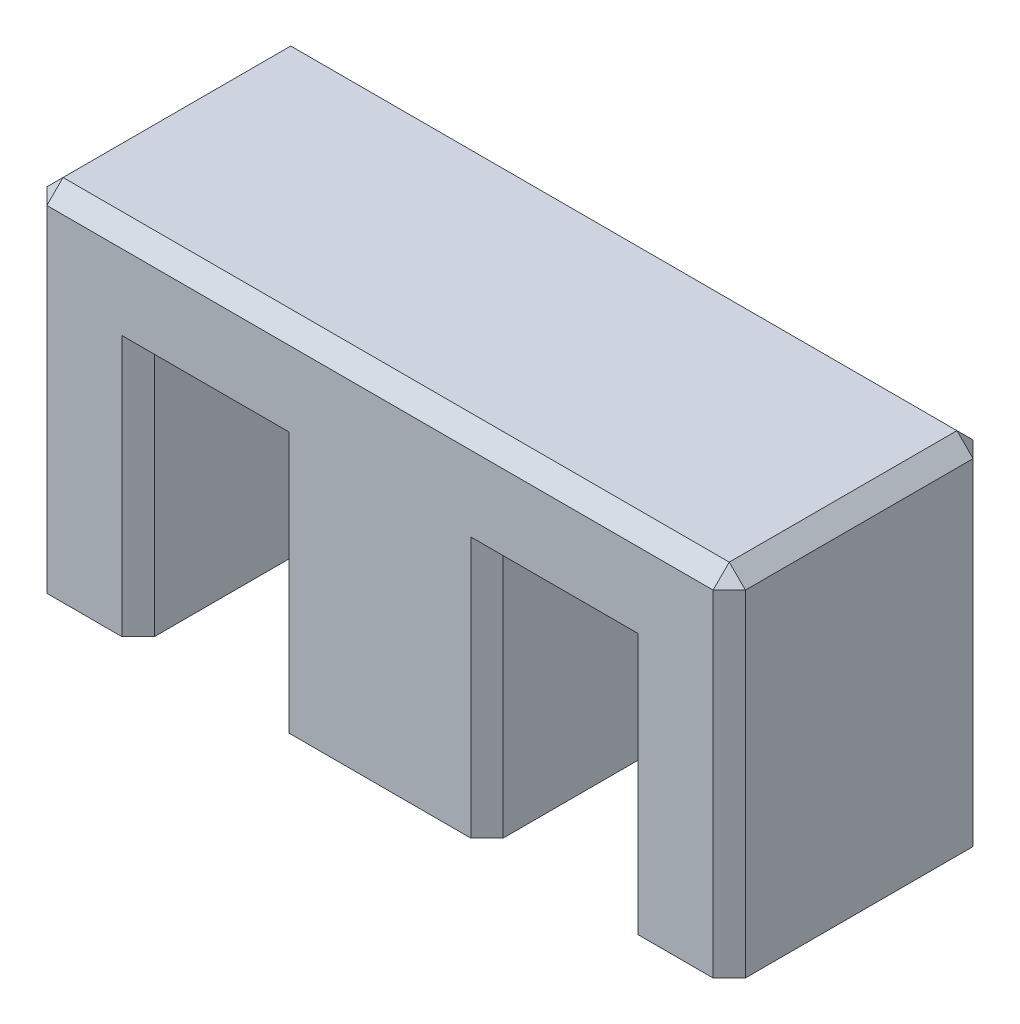
SolidWorks part; units mm, degrees
material "Ductile Iron"
ref_plane "Front Plane" through (0, 0, 0) normal (0, 0, 1) x (1, 0, 0)
ref_plane "Top Plane" through (0, 0, 0) normal (0, 1, 0) x (1, 0, 0)
ref_plane "Right Plane" through (0, 0, 0) normal (1, 0, 0) x (0, 0, -1)
sketch "Sketch1" plane through (0, 0, 0) normal (0, 0, 1) x (1, 0, 0)
  line L0 (0, 33.0544) -> (0, -29.4507) construction
  line L1 (43.25, 31.1735) -> (-43.25, 31.1735)
  line L2 (-43.25, 31.1735) -> (-43.25, -12.4265)
  line L3 (-43.25, -12.4265) -> (-29.95, -12.4265)
  line L4 (-29.95, -12.4265) -> (-29.95, 17.8735)
  line L5 (-29.95, 17.8735) -> (-13.25, 17.8735)
  line L6 (-13.25, 17.8735) -> (-13.25, -12.4265)
  line L7 (-13.25, -12.4265) -> (13.25, -12.4265)
  line L8 (13.25, 17.8735) -> (13.25, -12.4265)
  line L9 (29.95, 17.8735) -> (13.25, 17.8735)
  line L10 (29.95, -12.4265) -> (29.95, 17.8735)
  line L11 (43.25, -12.4265) -> (29.95, -12.4265)
  line L12 (43.25, 31.1735) -> (43.25, -12.4265)
  point P12 (0, -12.4265)
  point P13 (0, 31.1735)
  dimension "D1" = 86.5
  dimension "D2" = 43.6
  dimension "D3" = 26.5
  dimension "D4" = 13.3
  dimension "D5" = 13.3
extrude "Boss-Extrude1" add sketch "Sketch1" along normal mid plane 32.2
chamfer "Chamfer1" distance 2 angle 45 20 edges at (43.25, 31.1735, 0) (43.25, 9.3735, 16.1) (0, 31.1735, 16.1) (-43.25, 9.3735, 16.1) (-43.25, 31.1735, 0) (-43.25, 9.3735, -16.1) (0, 31.1735, -16.1) (43.25, 9.3735, -16.1) (13.25, 2.7235, -16.1) (29.95, 2.7235, -16.1) (21.6, 17.8735, -16.1) (-29.95, 2.7235, -16.1) (-13.25, 2.7235, -16.1) (-21.6, 17.8735, -16.1) (29.95, 2.7235, 16.1) (13.25, 2.7235, 16.1) (21.6, 17.8735, 16.1) (-29.95, 2.7235, 16.1) (-13.25, 2.7235, 16.1) (-21.6, 17.8735, 16.1)
